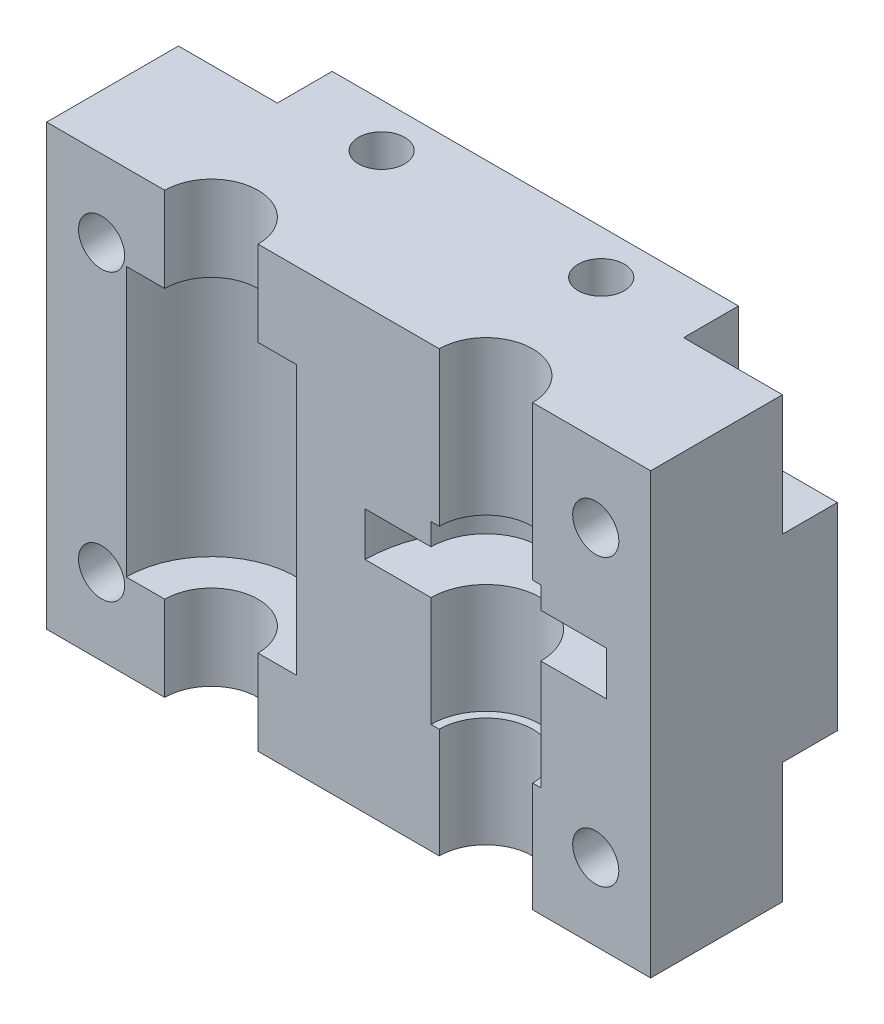
SolidWorks part; units mm, degrees
ref_plane "Plan de face" through (0, 0, 0) normal (0, 0, 1) x (1, 0, 0)
ref_plane "Plan de dessus" through (0, 0, 0) normal (0, 1, 0) x (1, 0, 0)
ref_plane "Plan de droite" through (0, 0, 0) normal (1, 0, 0) x (0, 0, -1)
sketch "Esquisse1" plane through (0, 0, 0) normal (0, 0, 1) x (1, 0, 0)
  line L1 (-27.5, -22.5) -> (27.5, -22.5)
  line L2 (-27.5, -22.5) -> (-27.5, 22.5)
  line L3 (-27.5, 22.5) -> (27.5, 22.5)
  line L4 (27.5, -22.5) -> (27.5, 22.5)
  line L5 (-27.5, -22.5) -> (27.5, 22.5) construction
  line L6 (-27.5, 22.5) -> (27.5, -22.5) construction
  point P0 (0, 0)
  dimension "D1" = 55
  dimension "D2" = 45
extrude "Boss.-Extru.1" add sketch "Esquisse1" along normal blind 12
sketch "Esquisse2" plane through (0, 22.5, 0) normal (0, 1, 0) x (1, 0, 0)
  line L0 (27.5, -12) -> (-27.5, -12) construction
  line L1 (-27.5, -12) -> (-27.5, 0) construction
  line L2 (27.5, -12) -> (27.5, 0) construction
  circle A0 centre (-12.5, -12) radius 4.25
  circle A1 centre (12.5, -12) radius 4.25
  dimension "D1" = 8.5
  dimension "D3" = 8.5
  dimension "D2" = 15
  dimension "D4" = 15
extrude "Enlèv. mat.-Extru.1" cut sketch "Esquisse2" against normal through all
sketch "Esquisse3" plane through (0, 0, 0) normal (0, 1, 0) x (1, 0, 0)
  circle A0 centre (-12.5, -12) radius 7.75
  dimension "D1" = 15.5
extrude "Enlèv. mat.-Extru.2" cut sketch "Esquisse3" against normal blind 12.25 and the other way blind 12.25
sketch "Esquisse9" plane through (0, 0, 12) normal (0, 0, 1) x (1, 0, 0)
  line L0 (-8.25, -22.5) -> (8.25, -22.5) construction
  line L1 (-30.9208, -30.2281) -> (30.1419, -30.2281)
  line L2 (-30.9208, -30.2281) -> (-30.9208, -18)
  line L3 (-30.9208, -18) -> (30.1419, -18)
  line L4 (30.1419, -30.2281) -> (30.1419, -18)
  line L5 (8.25, 22.5) -> (-8.25, 22.5) construction
  line L6 (31.3881, 26.1002) -> (-28.039, 26.1002)
  line L7 (31.3881, 26.1002) -> (31.3881, 18)
  line L8 (31.3881, 18) -> (-28.039, 18)
  line L9 (-28.039, 26.1002) -> (-28.039, 18)
  dimension "D1" = 4.5
  dimension "D2" = 4.5
extrude "Enlèv. mat.-Extru.7" cut sketch "Esquisse9" against normal blind 31
sketch "Sketch1" plane through (0, 0, 0) normal (0, 0, -1) x (-1, 0, 0)
  line L4 (-27.5, -18) -> (27.5, -18)
  line L5 (27.5, -18) -> (27.5, 18)
  line L6 (27.5, 18) -> (-27.5, 18)
  line L7 (-27.5, 18) -> (-27.5, -18)
  line L8 (-27.5, -18) -> (27.5, -18)
  line L9 (27.5, -18) -> (27.5, 18)
  line L10 (27.5, 18) -> (-27.5, 18)
  line L11 (-27.5, 18) -> (-27.5, -18)
  dimension "D1" = 0
extrude "Boss-Extrude1" add sketch "Sketch1" along normal blind 5
sketch "Sketch2" plane through (0, 0, 12) normal (0, 0, 1) x (1, 0, 0)
  line L0 (-27.5, 18) -> (-16.75, 18) construction
  line L1 (-27.5, 18) -> (-27.5, -18) construction
  line L2 (0, 18) -> (0, -18) construction
  line L3 (-8.25, 18) -> (8.25, 18) construction
  line L4 (8.25, -18) -> (-8.25, -18) construction
  line L5 (-27.5, 0) -> (27.5, 0) construction
  line L6 (27.5, -18) -> (27.5, 18) construction
  circle A0 centre (-22.5, 13) radius 2.1
  circle A1 centre (22.5, 13) radius 2.1
  circle A2 centre (22.5, -13) radius 2.1
  circle A3 centre (-22.5, -13) radius 2.1
  dimension "D1" = 4.2
  dimension "D2" = 5
  dimension "D3" = 5
extrude "Cut-Extrude1" cut sketch "Sketch2" against normal through all
sketch "Sketch3" plane through (0, 0, -5) normal (0, 0, -1) x (-1, 0, 0)
  circle A0 centre (-22.5, 13) radius 4
  circle A1 centre (22.5, 13) radius 4
  circle A2 centre (22.5, -13) radius 4
  circle A3 centre (-22.5, -13) radius 4
  dimension "D1" = 8
extrude "Cut-Extrude2" cut sketch "Sketch3" against normal blind 10
sketch "Sketch4" plane through (0, 0, -5) normal (0, 0, -1) x (-1, 0, 0)
  line L0 (-18.5, 13) -> (-18.5, 18)
  line L1 (-22.5, 9) -> (-27.5, 9)
  line L2 (-22.5, -9) -> (-27.5, -9)
  line L3 (-18.5, -13) -> (-18.5, -18)
  line L4 (-27.5, 18) -> (-27.5, -18)
  line L5 (-27.5, -18) -> (27.5, -18)
  line L6 (27.5, -18) -> (27.5, 18)
  line L7 (27.5, 18) -> (-27.5, 18)
  line L8 (-27.5, 18) -> (-27.5, 9)
  line L9 (-27.5, -18) -> (-18.5, -18)
  line L10 (27.5, -18) -> (27.5, -9)
  line L11 (27.5, 18) -> (18.5, 18)
  line L12 (18.5, -13) -> (18.5, -18)
  line L13 (22.5, -9) -> (27.5, -9)
  line L14 (22.5, 9) -> (27.5, 9)
  line L15 (18.5, 13) -> (18.5, 18)
  line L16 (-18.5, 18) -> (-27.5, 18)
  line L17 (-27.5, -9) -> (-27.5, -18)
  line L18 (18.5, -18) -> (27.5, -18)
  line L19 (27.5, 9) -> (27.5, 18)
  circle A0 centre (-22.5, 13) radius 4 construction
  circle A1 centre (-22.5, -13) radius 4 construction
  circle A2 centre (22.5, -13) radius 4 construction
  circle A3 centre (22.5, 13) radius 4 construction
  arc A4 (-18.5, 13) -> (-22.5, 9) centre (-22.5, 13) ccw
  arc A5 (-22.5, -9) -> (-18.5, -13) centre (-22.5, -13) ccw
  arc A6 (18.5, -13) -> (22.5, -9) centre (22.5, -13) ccw
  arc A7 (22.5, 9) -> (18.5, 13) centre (22.5, 13) ccw
  dimension "D1" = 0
extrude "Cut-Extrude3" cut sketch "Sketch4" against normal blind 5
sketch "Sketch5" plane through (0, 18, 0) normal (0, 1, 0) x (1, 0, 0)
  line L0 (-27.5, -12) -> (-27.5, 0) construction
  line L1 (27.5, 0) -> (27.5, 5) construction
  line L2 (-18.5, 5) -> (18.5, 5) construction
  circle A0 centre (-10, 1) radius 2.1
  circle A1 centre (10, 1) radius 2.1
  dimension "D1" = 4.2
  dimension "D2" = 4.2
  dimension "D3" = 17.5
  dimension "D4" = 17.5
  dimension "D5" = 4
  dimension "D6" = 4
extrude "Cut-Extrude4" cut sketch "Sketch5" against normal through all
sketch "Sketch7" plane through (0, 18, 0) normal (0, 1, 0) x (1, 0, 0)
  line L10 (18.5, 5) -> (-18.5, 5)
  line L11 (-18.5, 5) -> (-18.5, 0)
  line L12 (-18.5, 0) -> (-27.5, 0)
  line L13 (-27.5, 0) -> (-27.5, -12)
  line L14 (-27.5, -12) -> (-16.75, -12)
  line L15 (-8.25, -12) -> (8.25, -12)
  line L16 (16.75, -12) -> (27.5, -12)
  line L17 (27.5, -12) -> (27.5, 0)
  line L18 (27.5, 0) -> (18.5, 0)
  line L19 (18.5, 0) -> (18.5, 5)
  line L20 (18.5, 5) -> (-18.5, 5)
  line L21 (-18.5, 5) -> (-18.5, 0)
  line L22 (-18.5, 0) -> (-27.5, 0)
  line L23 (-27.5, 0) -> (-27.5, -12)
  line L24 (-27.5, -12) -> (-16.75, -12)
  line L25 (-8.25, -12) -> (8.25, -12)
  line L26 (16.75, -12) -> (27.5, -12)
  line L27 (27.5, -12) -> (27.5, 0)
  line L28 (27.5, 0) -> (18.5, 0)
  line L29 (18.5, 0) -> (18.5, 5)
  circle A0 centre (10, 1) radius 2.1 construction
  circle A1 centre (-10, 1) radius 2.1 construction
  arc A2 (-8.25, -12) -> (-16.75, -12) centre (-12.5, -12) ccw
  arc A3 (16.75, -12) -> (8.25, -12) centre (12.5, -12) ccw
  arc A4 (-8.25, -12) -> (-16.75, -12) centre (-12.5, -12) ccw
  arc A5 (16.75, -12) -> (8.25, -12) centre (12.5, -12) ccw
  circle A6 centre (10, 1) radius 2.1
  circle A7 centre (-10, 1) radius 2.1
  dimension "D1" = 0
extrude "Boss-Extrude4" add sketch "Sketch7" along normal blind 2
sketch "Sketch8" plane through (0, -18, 0) normal (0, -1, 0) x (1, 0, 0)
  line L10 (-27.5, 0) -> (-18.5, 0)
  line L11 (-18.5, 0) -> (-18.5, -5)
  line L12 (-18.5, -5) -> (18.5, -5)
  line L13 (18.5, -5) -> (18.5, 0)
  line L14 (18.5, 0) -> (27.5, 0)
  line L15 (27.5, 0) -> (27.5, 12)
  line L16 (27.5, 12) -> (16.75, 12)
  line L17 (8.25, 12) -> (-8.25, 12)
  line L18 (-16.75, 12) -> (-27.5, 12)
  line L19 (-27.5, 12) -> (-27.5, 0)
  line L20 (-27.5, 0) -> (-18.5, 0)
  line L21 (-18.5, 0) -> (-18.5, -5)
  line L22 (-18.5, -5) -> (18.5, -5)
  line L23 (18.5, -5) -> (18.5, 0)
  line L24 (18.5, 0) -> (27.5, 0)
  line L25 (27.5, 0) -> (27.5, 12)
  line L26 (27.5, 12) -> (16.75, 12)
  line L27 (8.25, 12) -> (-8.25, 12)
  line L28 (-16.75, 12) -> (-27.5, 12)
  line L29 (-27.5, 12) -> (-27.5, 0)
  circle A0 centre (-10, -1) radius 2.1 construction
  circle A1 centre (10, -1) radius 2.1 construction
  arc A2 (8.25, 12) -> (16.75, 12) centre (12.5, 12) ccw
  arc A3 (-16.75, 12) -> (-8.25, 12) centre (-12.5, 12) ccw
  arc A4 (8.25, 12) -> (16.75, 12) centre (12.5, 12) ccw
  arc A5 (-16.75, 12) -> (-8.25, 12) centre (-12.5, 12) ccw
  circle A6 centre (10, -1) radius 2.1
  circle A7 centre (-10, -1) radius 2.1
  dimension "D1" = 0
extrude "Boss-Extrude5" add sketch "Sketch8" along normal blind 2
sketch "Sketch9" plane through (0, 0, -5) normal (0, 0, -1) x (-1, 0, 0)
  line L0 (-27.5, 20) -> (-27.5, 9) construction
  line L1 (-13.5, 16) -> (-6.5, 16)
  line L2 (-13.5, 16) -> (-13.5, 12.8)
  line L3 (-13.5, 12.8) -> (-6.5, 12.8)
  line L4 (-6.5, 16) -> (-6.5, 12.8)
  line L5 (-18.5, 20) -> (18.5, 20) construction
  line L6 (0, 20) -> (0, -9.1772) construction
  line L7 (13.5, 12.8) -> (6.5, 12.8)
  line L8 (6.5, 16) -> (6.5, 12.8)
  line L9 (13.5, 16) -> (6.5, 16)
  line L10 (13.5, 16) -> (13.5, 12.8)
  line L11 (-27.5, 0) -> (-8.3783, 0) construction
  line L12 (-27.5, 9) -> (-27.5, -9) construction
  line L13 (13.5, -16) -> (13.5, -12.8)
  line L14 (13.5, -16) -> (6.5, -16)
  line L15 (6.5, -16) -> (6.5, -12.8)
  line L16 (13.5, -12.8) -> (6.5, -12.8)
  line L17 (-13.5, -12.8) -> (-6.5, -12.8)
  line L18 (-6.5, -16) -> (-6.5, -12.8)
  line L19 (-13.5, -16) -> (-6.5, -16)
  line L20 (-13.5, -16) -> (-13.5, -12.8)
  point P4 (-10, 16)
  dimension "D1" = 7
  dimension "D2" = 17.5
  dimension "D3" = 4
  dimension "D4" = 3.2
extrude "Cut-Extrude6" cut sketch "Sketch9" against normal blind 8
ref_plane "Plane1" through (0, 0, 0) normal (-1, 0, 0) x (0, 0, 1)
ref_axis "Axis1" through (12.5, -20, 12) along (0, 1, 0)
sketch "Sketch10" plane through (0, 0, 12) normal (0, 0, 1) x (1, 0, 0)
  line L1 (0, 0) -> (24.1807, 0) construction
  line L2 (12.5, 20) -> (12.5, -20) construction
  line L3 (16.75, 20) -> (8.25, 20) construction
  line L4 (8.25, -20) -> (16.75, -20) construction
  line L6 (12.5, -10) -> (17.5, -10)
  line L7 (12.5, -10) -> (12.5, 0)
  line L8 (12.5, 0) -> (17.5, 0)
  line L9 (17.5, -10) -> (17.5, 0)
  line L10 (12.5, 0) -> (23.5, 0)
  line L11 (12.5, 0) -> (12.5, 4)
  line L12 (12.5, 4) -> (23.5, 4)
  line L13 (23.5, 0) -> (23.5, 4)
  line L14 (12.5, 4) -> (17.5, 4)
  line L15 (12.5, 4) -> (12.5, 6)
  line L16 (12.5, 6) -> (17.5, 6)
  line L17 (17.5, 4) -> (17.5, 6)
  point P9 (12.5, 0)
  dimension "D1" = 5
  dimension "D2" = 10
  dimension "D3" = 4
  dimension "D4" = 11
  dimension "D5" = 2
revolve "Cut-Revolve1" cut sketch "Sketch10" angle 360 about L2 region at (14.625, -5, 12) region at (17.125, -5, 12) region at (14.625, 2, 12) region at (20.125, 2, 12) region at (14.625, 5, 12) region at (17.125, 5, 12)
move or copy body "Body-Move/Copy1" [suppressed] bodies to move or copy 135
